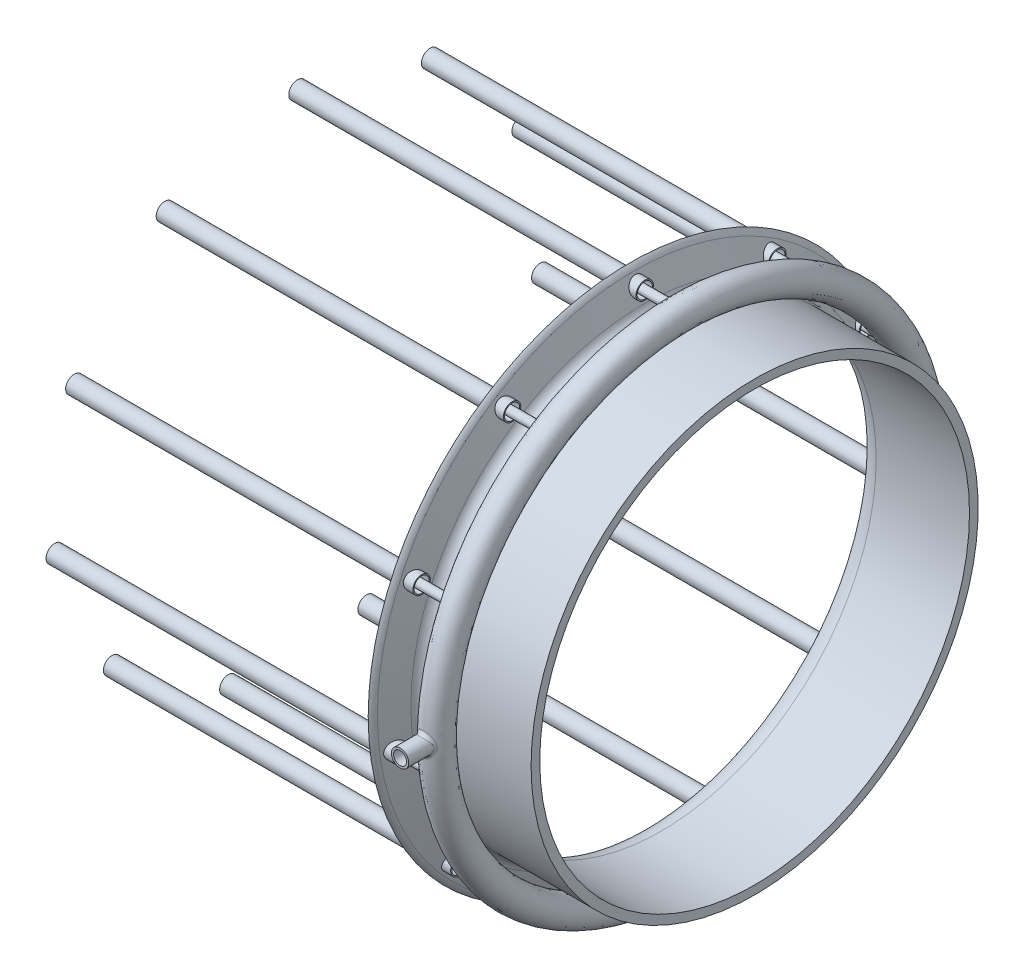
SolidWorks part; units mm, degrees
note: The reader was unsure of these and kept them because the rebuilt part matched: shared geometry of "Sketch3<2>", "Sketch10<2>", "Sketch11<2>".
material "AISI 316 Stainless Steel Sheet (SS)"
ref_plane "Front Plane" through (0, 0, 0) normal (0, 0, 1) x (1, 0, 0)
ref_plane "Top Plane" through (0, 0, 0) normal (0, 1, 0) x (1, 0, 0)
ref_plane "Right Plane" through (0, 0, 0) normal (1, 0, 0) x (0, 0, -1)
sketch "Sketch1" plane through (0, 0, 0) normal (0, 0, 1) x (1, 0, 0)
  line L0 (-489.6053, -55.5) -> (20274.6682, -55.5) construction
  line L3 (45.6801, 4) -> (45.6801, 6)
  line L5 (45.6801, 4) -> (49.3199, -6)
  line L6 (49.3199, -4) -> (74.3199, -4)
  line L7 (49.3199, -4) -> (49.3199, -6)
  line L8 (45.6801, 4) -> (45.6801, -0.6316) construction
  line L9 (49.3199, -6) -> (74.3199, -6)
  line L10 (74.3199, -4) -> (74.3199, -6)
  line L11 (45.6801, 6) -> (49.3199, -4)
revolve "Revolve1" add sketch "Sketch1" angle 360 about L0
fillet "Fillet1" radius 5 2 edges at (45.6801, -55.5, 59.5) (49.3199, -55.5, 49.5)
fillet "Fillet2" radius 3 2 edges at (45.6801, -55.5, 61.5) (49.3199, -55.5, 51.5)
ref_plane "Plane1" through (49, 0, 0) normal (1, 0, 0) x (0, 0, -1)
sketch "Sketch3" plane through (49, 0, 0) normal (1, 0, 0) x (0, 0, -1)
  circle A0 centre (0, 1) radius 2
  dimension "D2" = 4
  dimension "D1" = 1
extrude "Cut-Extrude1" cut sketch "Sketch3" against normal blind 10
sketch "Sketch6" plane through (0, 0, 0) normal (0, 0, 1) x (1, 0, 0)
  line L0 (-951.3986, -55.5) -> (49048.6014, -55.5) construction
  line L1 (48.6014, -2.0261) -> (48.6014, -108.9739) construction
  point P5 (48.6014, -55.5)
pattern_circular "CirPattern1" count 11 over 360 about axis through (0, -55.5, 0) along (1, 0, 0) of "Cut-Extrude1"
extrude "Boss-Extrude1" add sketch "Sketch3<2>" against normal blind 80
sketch "Sketch3<2>" plane through (49, 0, 0) normal (1, 0, 0) x (0, 0, -1) same geometry as "Sketch3"
pattern_circular "CirPattern2" count 11 over 360 about axis through (0, -55.5, 0) along (1, 0, 0) of "Boss-Extrude1"
sketch "Sketch8" plane through (0, 0, 0) normal (0, 0, 1) x (1, 0, 0)
  circle A0 centre (57.5783, 0.9184) radius 2
  ellipse E0 centre (57.5783, 0.9184) end of major axis (57.5783, -2.3624) minor radius 3.0748
  dimension "D1" = 4
revolve "Revolve2" add sketch "Sketch8" angle 360 about L0
sketch "Sketch9" plane through (49, 0, 0) normal (1, 0, 0) x (0, 0, -1)
  circle A0 centre (0, 1) radius 1.75
  circle A1 centre (0, 1) radius 2 construction
  dimension "D1" = 3.5
extrude "Cut-Extrude2" cut sketch "Sketch9" against normal blind 90
pattern_circular "CirPattern3" count 11 over 360 about axis through (0, -55.5, 0) along (1, 0, 0) of "Cut-Extrude2"
ref_plane "Plane2" through (55.8, 0, 0) normal (1, 0, 0) x (0, 0, -1)
sketch "Sketch10" plane through (55.8, 0, 0) normal (1, 0, 0) x (0, 0, -1)
  circle A0 centre (0, 1) radius 1
  circle A1 centre (0, 1) radius 1.75 construction
  circle A2 centre (0, 1) radius 0.7331
  dimension "D1" = 2
extrude "Boss-Extrude3" add sketch "Sketch10" against normal blind 60
pattern_circular "CirPattern4" count 11 over 360 about axis through (0, -55.5, 0) along (1, 0, 0) of "Boss-Extrude3"
fillet "Fillet3" radius 0.3 1 edges at (55.5966, 0.6405, 0.9331)
fillet "Fillet4" radius 0.4 1 edges at (54.6697, 1.9823, 0.1876)
extrude "Cut-Extrude3" cut sketch "Sketch10<2>" against normal blind 60 contours A2
sketch "Sketch10<2>" plane through (55.8, 0, 0) normal (1, 0, 0) x (0, 0, -1) same geometry as "Sketch10"
ref_plane "Plane3" through (0, -55.5, 0) normal (0, 1, 0) x (1, 0, 0)
ref_plane "Plane4" through (0, 0, 65) normal (0, 0, 1) x (1, 0, 0)
sketch "Sketch11" plane through (0, 0, 65) normal (0, 0, 1) x (1, 0, 0)
  line L0 (-200951.3986, -55.5) -> (249048.6014, -55.5) construction
  line L1 (46.5409, -114.635) -> (46.5409, 3.635) construction
  circle A0 centre (57.6409, -55.5) radius 2
  circle A1 centre (57.6409, -55.5) radius 1.5
  dimension "D1" = 4
  dimension "D3" = 3
  dimension "D2" = 11.1
extrude "Cut-Extrude7" cut sketch "Sketch11" against normal blind 8 contours A1
extrude "Boss-Extrude4" add sketch "Sketch11<2>" against normal up to body separate body
sketch "Sketch11<2>" plane through (0, 0, 65) normal (0, 0, 1) x (1, 0, 0) same geometry as "Sketch11"
fillet "Fillet5" radius 0.8 1 edges at (55.6694, -55.8362, 58.9895)
